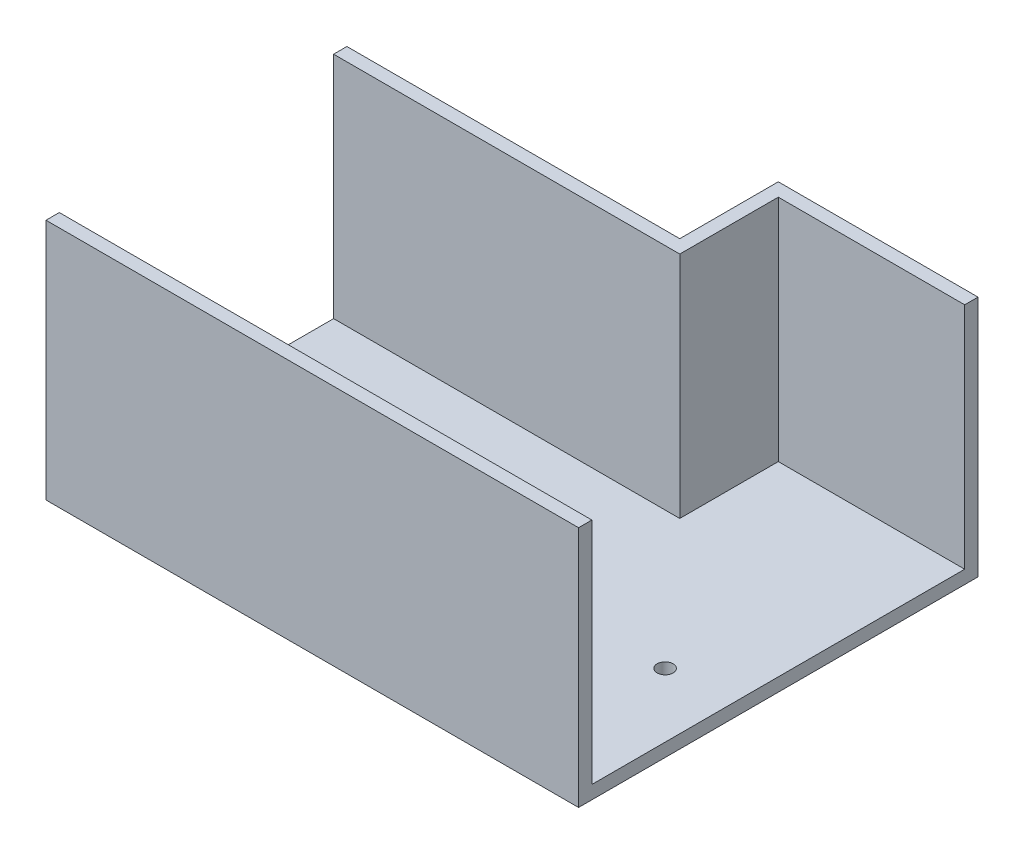
SolidWorks part; units mm, degrees
ref_plane "Front Plane" through (0, 0, 0) normal (0, 0, 1) x (1, 0, 0)
ref_plane "Top Plane" through (0, 0, 0) normal (0, 1, 0) x (1, 0, 0)
ref_plane "Right Plane" through (0, 0, 0) normal (1, 0, 0) x (0, 0, -1)
sketch "Szkic1" plane through (0, 0, 0) normal (0, 1, 0) x (1, 0, 0)
  line L0 (91.2344, 21.5) -> (70.2344, 21.5)
  line L1 (91.2344, -30) -> (-108.7656, -30)
  line L2 (91.2344, -30) -> (91.2344, 73)
  line L3 (91.2344, 73) -> (-108.7656, 73)
  line L4 (-108.7656, -30) -> (-108.7656, 73)
  line L5 (91.2344, -30) -> (-108.7656, 73) construction
  line L6 (91.2344, 73) -> (-108.7656, -30) construction
  line L7 (67.2344, 21.5) -> (67.2344, 110)
  line L8 (67.2344, 110) -> (91.2344, 110)
  line L9 (91.2344, 110) -> (91.2344, 73)
  line L10 (91.2344, 110) -> (21.2344, 110)
  line L11 (21.2344, 110) -> (21.2344, 73)
  line L12 (21.2344, 110) -> (21.2344, 115)
  line L13 (21.2344, 115) -> (91.2344, 115)
  line L14 (91.2344, 115) -> (91.2344, 110)
  line L15 (21.2344, 115) -> (16.2344, 115)
  line L16 (16.2344, 115) -> (16.2344, 73)
  line L17 (16.2344, 73) -> (16.2344, 78)
  line L18 (91.2344, -30) -> (91.2344, -35)
  line L19 (91.2344, -35) -> (-108.7656, -35)
  line L20 (16.2344, 78) -> (-108.7656, 78)
  line L21 (-108.7656, 78) -> (-108.7656, 73)
  line L22 (-108.7656, -35) -> (-108.7656, -30)
  line L23 (91.2344, -35) -> (91.2344, -30)
  circle A0 centre (67.2344, 21.5) radius 3
  point P0 (-8.7656, 21.5)
  dimension "D4" = 6
  dimension "D7" = 5
  dimension "D1" = 103
  dimension "D2" = 200
  dimension "D3" = 21
  dimension "D5" = 5
  dimension "D6" = 70
extrude "Dodanie-wyciągnięcie1" add sketch "Szkic1" against normal blind 5 contours L22 L19 L18 L1 | L10 L11 L3 L7 | L9 L8 L7 L3 | L20 L21 L3 L16 | L15 L16 L3 L11 L12 | L14 L13 L12 L10 L8 | A0 L7 L3 L4 L1 L2 L0 | A0 L0 L2 L3 L7 region at (-14.4716, 0, -19.855) region at (79.2961, 0, -47.3908) region at (-8.7656, 0, 32.5) region at (79.2344, 0, -91.5) region at (44.2344, 0, -91.5) region at (56.2344, 0, -112.5) region at (-46.2656, 0, -75.5) region at (18.7344, 0, -94)
extrude "Dodanie-wyciągnięcie2" add sketch "Szkic1<4>" along normal blind 86 contours L20 L21 L3 L16 | L15 L16 L3 L11 L12 | L14 L13 L12 L10 L8 | L22 L19 L18 L1 region at (-8.7656, 0, 32.5) region at (56.2344, 0, -112.5) region at (-46.2656, 0, -75.5) region at (18.7344, 0, -94)
sketch "Szkic1<4>" plane through (0, 0, 0) normal (0, 1, 0) x (1, 0, 0) same geometry as "Szkic1"
